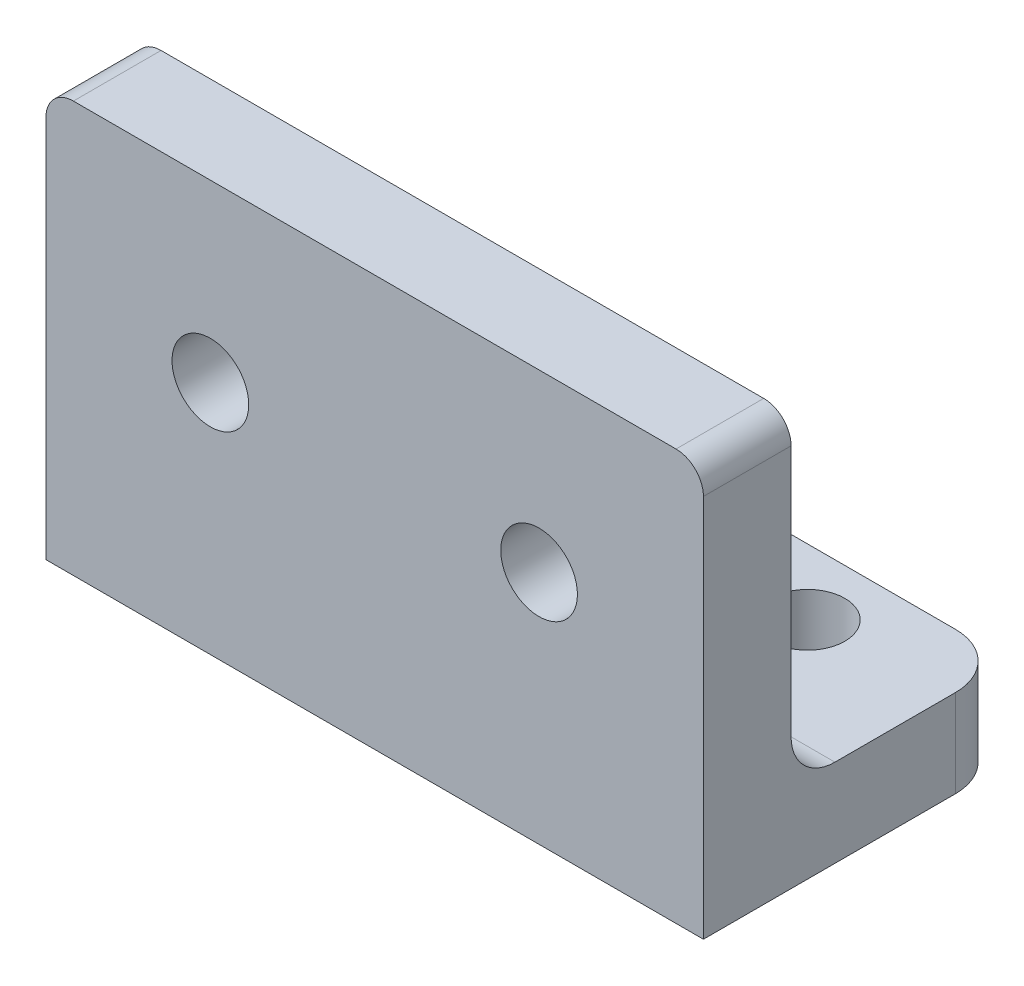
SolidWorks part; units mm, degrees
ref_plane "Front Plane" through (0, 0, 0) normal (0, 0, 1) x (1, 0, 0)
ref_plane "Top Plane" through (0, 0, 0) normal (0, 1, 0) x (1, 0, 0)
ref_plane "Right Plane" through (0, 0, 0) normal (1, 0, 0) x (0, 0, -1)
sketch "Sketch1" plane through (0, 0, 0) normal (0, 0, 1) x (1, 0, 0)
  line L1 (-15, 9.375) -> (15, 9.375)
  line L2 (-15, 9.375) -> (-15, -9.375)
  line L3 (-15, -9.375) -> (15, -9.375)
  line L4 (15, 9.375) -> (15, -9.375)
  line L5 (-15, 9.375) -> (15, -9.375) construction
  line L6 (-15, -9.375) -> (15, 9.375) construction
  point P0 (0, 0)
  dimension "D1" = 30
  dimension "D2" = 18.75
extrude "Boss-Extrude1" add sketch "Sketch1" along normal blind 4
fillet "Fillet1" radius 1.25 2 edges at (15, 9.375, 2) (-15, 9.375, 2)
sketch "Sketch3" plane through (0, 0, 4) normal (0, 0, 1) x (1, 0, 0)
  circle A0 centre (-7.5, 1.375) radius 1.75
  circle A1 centre (7.5, 1.375) radius 1.75
extrude "Cut-Extrude1" cut sketch "Sketch3" against normal blind 10
sketch "Sketch4" plane through (0, 0, 0) normal (0, 0, -1) x (-1, 0, 0)
  line L0 (15, 8.125) -> (15, -9.375) construction
  line L1 (-15, -9.375) -> (15, -9.375)
  line L2 (-15, -9.375) -> (-15, -5.375)
  line L3 (-15, -5.375) -> (15, -5.375)
  line L4 (15, -9.375) -> (15, -5.375)
  dimension "D1" = 4
extrude "Boss-Extrude2" add sketch "Sketch4" along normal blind 10
fillet "Fillet2" radius 2.5 2 edges at (15, -7.375, -10) (-15, -7.375, -10)
fillet "Fillet3" radius 2 1 edges at (0, -5.375, 0)
hole_wizard "M3 Clearance Hole1" positions "Sketch5" profile "Sketch6" hole size "M3" standard "ISO"
sketch "Sketch5" plane through (0, -9.375, 0) normal (0, -1, 0) x (-1, 0, 0)
  line L0 (-8.75, 10) -> (-8.75, 7) construction
  line L1 (-12.5, 10) -> (12.5, 10) construction
  line L5 (0, 0) -> (0, 10) construction
  line L7 (-8.75, 7) -> (0, 7) construction
  line L9 (0, 7) -> (8.75, 7) construction
  point P0 (-8.75, 7)
  point P2 (8.75, 7)
  dimension "D1" = 3
  dimension "D2" = 8.75
sketch "Sketch6" plane through (8.75, -9.375, -7) normal (1, 0, 0) x (0, 0, -1)
  line L0 (0, 0) -> (0, 17.0215)
  line L1 (0, 17.0215) -> (1.7, 16)
  line L2 (1.7, 16) -> (1.7, 0)
  line L5 (1.7, 0) -> (0, 0)
  line L10 (0, 17.0215) -> (-1.7, 16) construction
  line L11 (0, -6.35) -> (0, 107.95) construction
  dimension "Hole Dia." = 3.4
  dimension "Hole Depth" = 16
  dimension "Drill Angle" = 118
